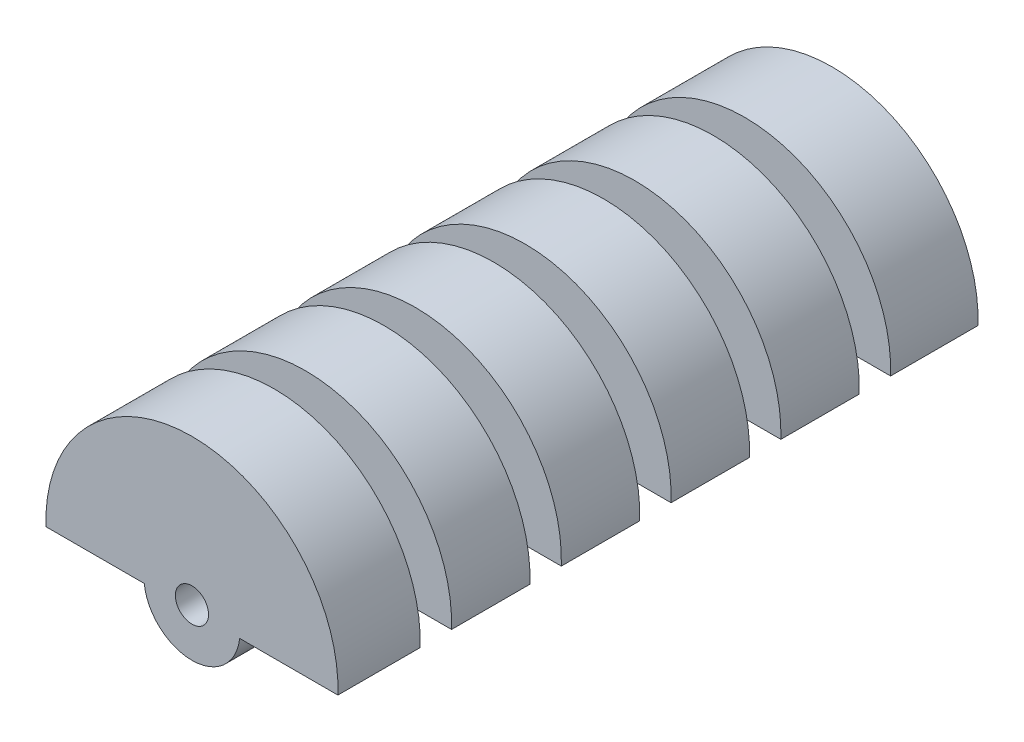
SolidWorks part; units mm, degrees
material "RUBBER 65A Test Modulus"
ref_plane "Front Plane" through (0, 0, 0) normal (0, 0, 1) x (1, 0, 0)
ref_plane "Top Plane" through (0, 0, 0) normal (0, 1, 0) x (1, 0, 0)
ref_plane "Right Plane" through (0, 0, 0) normal (1, 0, 0) x (0, 0, -1)
sketch "Sketch3" plane through (0, 0, 0) normal (0, 0, 1) x (1, 0, 0)
  circle A0 centre (0, 0) radius 27.94
  dimension "D1" = 55.88
extrude "Boss-Extrude2" add sketch "Sketch3" along normal blind 122.46
ref_axis "Axis2" through (0, 0, 121.5887) along (0, 0, -1)
sketch "Sketch5" plane through (0, 0, 122.46) normal (0, 0, 1) x (1, 0, 0)
  circle A0 centre (0, 0) radius 3.175
  dimension "D1" = 6.35
extrude "Cut-Extrude1" cut sketch "Sketch5" against normal through all contours A0
sketch "Sketch4" plane through (0, 0, 0) normal (0, 1, 0) x (1, 0, 0)
  line L0 (0, -122.46) -> (0, 0) construction
  line L1 (-27.94, -122.46) -> (27.94, -122.46) construction
  line L3 (-27.94, -106.72) -> (-13.94, -106.72)
  line L4 (-27.94, -106.72) -> (-27.94, -100.72)
  line L5 (-27.94, -100.72) -> (-13.94, -100.72)
  line L6 (-13.94, -106.72) -> (-13.94, -100.72)
  line L63 (-27.94, -85.72) -> (-27.94, -79.72)
  line L64 (-27.94, -85.72) -> (-13.94, -85.72)
  line L65 (-13.94, -85.72) -> (-13.94, -79.72)
  line L66 (-27.94, -79.72) -> (-13.94, -79.72)
  line L67 (-27.94, -64.72) -> (-27.94, -58.72)
  line L68 (-27.94, -64.72) -> (-13.94, -64.72)
  line L69 (-13.94, -64.72) -> (-13.94, -58.72)
  line L70 (-27.94, -58.72) -> (-13.94, -58.72)
  line L71 (-27.94, -43.72) -> (-27.94, -37.72)
  line L72 (-27.94, -43.72) -> (-13.94, -43.72)
  line L73 (-13.94, -43.72) -> (-13.94, -37.72)
  line L74 (-27.94, -37.72) -> (-13.94, -37.72)
  line L75 (-27.94, -22.72) -> (-27.94, -16.72)
  line L76 (-27.94, -22.72) -> (-13.94, -22.72)
  line L77 (-13.94, -22.72) -> (-13.94, -16.72)
  line L78 (-27.94, -16.72) -> (-13.94, -16.72)
  line L91 (-27.94, -106.72) -> (-27.94, -85.72) construction
  line L92 (-27.94, -1.72) -> (-27.94, 4.28) [skipped]
  line L93 (-27.94, -1.72) -> (-13.94, -1.72) [skipped]
  line L94 (-13.94, -1.72) -> (-13.94, 4.28) [skipped]
  line L95 (-27.94, 4.28) -> (-13.94, 4.28) [skipped]
  line L96 (-27.94, 19.28) -> (-27.94, 25.28) [skipped]
  line L97 (-27.94, 19.28) -> (-13.94, 19.28) [skipped]
  line L98 (-13.94, 19.28) -> (-13.94, 25.28) [skipped]
  line L99 (-27.94, 25.28) -> (-13.94, 25.28) [skipped]
  line L100 (-27.94, 40.28) -> (-27.94, 46.28) [skipped]
  line L101 (-27.94, 40.28) -> (-13.94, 40.28) [skipped]
  line L102 (-13.94, 40.28) -> (-13.94, 46.28) [skipped]
  line L103 (-27.94, 46.28) -> (-13.94, 46.28) [skipped]
  dimension "D1" = 15.74
  dimension "D2" = 6
  dimension "D3" = 27.94
  dimension "D4" = 14
  dimension "D6" = 21
  dimension "D5" = 8
revolve "Cut-Revolve1" cut sketch "Sketch4" angle 360 about L0
shell "Shell1" thickness 3
sketch "Sketch10" plane through (0, 0, 0) normal (0, 0, -1) x (-1, 0, 0)
  line L0 (0, 27.94) -> (0, -27.94) construction
  line L1 (-27.94, 0) -> (27.94, 0) construction
  line L2 (-1, 27.9221) -> (-1, 3.0134)
  line L3 (1, 3.0134) -> (1, 27.9221)
  line L4 (3.0134, 1) -> (27.9221, 1)
  line L5 (3.0134, -1) -> (27.9221, -1)
  line L6 (-1, -3.0134) -> (-1, -27.9221)
  line L7 (1, -3.0134) -> (1, -27.9221)
  line L8 (-27.9221, -1) -> (-3.0134, -1)
  line L9 (-27.9221, 1) -> (-3.0134, 1)
  circle A0 centre (0, 0) radius 27.94 construction
  circle A1 centre (0, 0) radius 3.175 construction
  arc A2 (-1, -27.9221) -> (1, -27.9221) centre (0, 0) ccw
  arc A3 (27.9221, -1) -> (27.9221, 1) centre (0, 0) ccw
  arc A4 (1, 27.9221) -> (-1, 27.9221) centre (0, 0) ccw
  arc A5 (-27.9221, 1) -> (-27.9221, -1) centre (0, 0) ccw
  arc A6 (-1, -3.0134) -> (1, -3.0134) centre (0, 0) ccw
  arc A7 (-3.0134, 1) -> (-3.0134, -1) centre (0, 0) ccw
  arc A8 (1, 3.0134) -> (-1, 3.0134) centre (0, 0) ccw
  arc A9 (3.0134, -1) -> (3.0134, 1) centre (0, 0) ccw
  dimension "D1" = 1
  dimension "D2" = 1
  dimension "D3" = 1
  dimension "D4" = 1
  dimension "D5" = 1
extrude "Boss-Extrude3" add sketch "Sketch10" against normal up to surface (122.46 mm away) up to face at (3.175, 0, 122.46)
ref_plane "Plane1" through (0, 0, 0) normal (-0.7071, -0.7071, 0) x (0, 0, -1)
ref_plane "Plane2" through (0, 0, 0) normal (-0.7071, 0.7071, 0) x (0, 0, -1)
ref_plane "Plane3" through (0, 0, 0) normal (0, 1, 0) x (1, 0, 0)
sketch "Sketch13" plane through (0, 0, 0) normal (0, 1, 0) x (1, 0, 0)
  line L0 (-30.3872, -37.72) -> (-13.9041, -37.72)
  line L1 (-30.3872, -16.72) -> (-13.9041, -16.72)
  line L2 (-30.3872, -16.72) -> (-30.3872, -22.72)
  line L3 (-30.3872, -22.72) -> (-13.9041, -22.72)
  line L4 (-13.9041, -16.72) -> (-13.9041, -22.72)
  line L5 (-30.3872, -37.72) -> (-30.3872, -43.72)
  line L6 (-30.3872, -43.72) -> (-13.9041, -43.72)
  line L7 (-13.9041, -37.72) -> (-13.9041, -43.72)
  line L8 (-30.3872, -58.72) -> (-13.9041, -58.72)
  line L9 (-30.3872, -58.72) -> (-30.3872, -64.72)
  line L10 (-30.3872, -64.72) -> (-13.9041, -64.72)
  line L11 (-13.9041, -58.72) -> (-13.9041, -64.72)
  line L12 (-30.3872, -79.72) -> (-13.9041, -79.72)
  line L13 (-30.3872, -79.72) -> (-30.3872, -85.72)
  line L14 (-30.3872, -85.72) -> (-13.9041, -85.72)
  line L15 (-13.9041, -79.72) -> (-13.9041, -85.72)
  line L16 (-30.3872, -100.72) -> (-13.9041, -100.72)
  line L17 (-30.3872, -100.72) -> (-30.3872, -106.72)
  line L18 (-30.3872, -106.72) -> (-13.9041, -106.72)
  line L19 (-13.9041, -100.72) -> (-13.9041, -106.72)
  dimension "D2" = 6
  dimension "D1" = 5
revolve "Cut-Revolve2" cut sketch "Sketch13" angle 360 about axis through (0, 0, 121.5887) along (0, 0, -1)
sketch "Sketch15" plane through (0, 0, 0) normal (0, 0, -1) x (-1, 0, 0)
  line L0 (0, 0) -> (0, 28.5004) construction
  line L1 (0, 0) -> (-22.0052, 22.0052) construction
sketch "Sketch16" plane through (0, 0, 0) normal (0, 0, -1) x (-1, 0, 0)
  line L0 (-3.175, 0) -> (-6.9755, 0) construction
  line L1 (-27.94, 0) -> (27.94, 0) construction
  line L2 (3.175, 0) -> (7.175, 0) construction
  line L3 (-6.9755, 0) -> (-6.9755, -0.971) construction
  line L4 (-6.9755, -0.971) -> (-6.6911, -0.971) construction
  line L5 (7.175, 0) -> (7.175, -1) construction
  line L8 (-3.175, 0) -> (-6.175, 0) construction
  line L9 (3.175, 0) -> (6.175, 0) construction
  line L10 (-27.9231, -0.971) -> (-6.0982, -0.971)
  line L11 (27.9221, -1) -> (6.0935, -1)
  arc A0 (-27.9231, -0.971) -> (27.9221, -1) centre (0, 0) ccw
  circle A1 centre (0, 0) radius 27.94 construction
  circle A2 centre (0, 0) radius 3.175 construction
  arc A5 (-6.0982, -0.971) -> (6.0935, -1) centre (0, 0) ccw
extrude "Cut-Extrude3" cut sketch "Sketch16" against normal blind 123
sketch "Sketch18" plane through (0, 0, 0) normal (0, 0, -1) x (-1, 0, 0)
  line L0 (-3.175, 0) -> (-9.175, 0)
  line L1 (3.175, 0) -> (9.175, 0)
  line L2 (-6.0982, -0.971) -> (-27.9231, -0.971) construction
  circle A0 centre (0, 0) radius 3.175 construction
  arc A1 (-3.175, 0) -> (3.175, 0) centre (0, 0) ccw
  arc A2 (-9.175, 0) -> (9.175, 0) centre (0, 0) ccw
extrude "Boss-Extrude5" add sketch "Sketch18" against normal blind 122.46
equation "\"inwall\"= .75"
equation "\"outwall\"=2"
